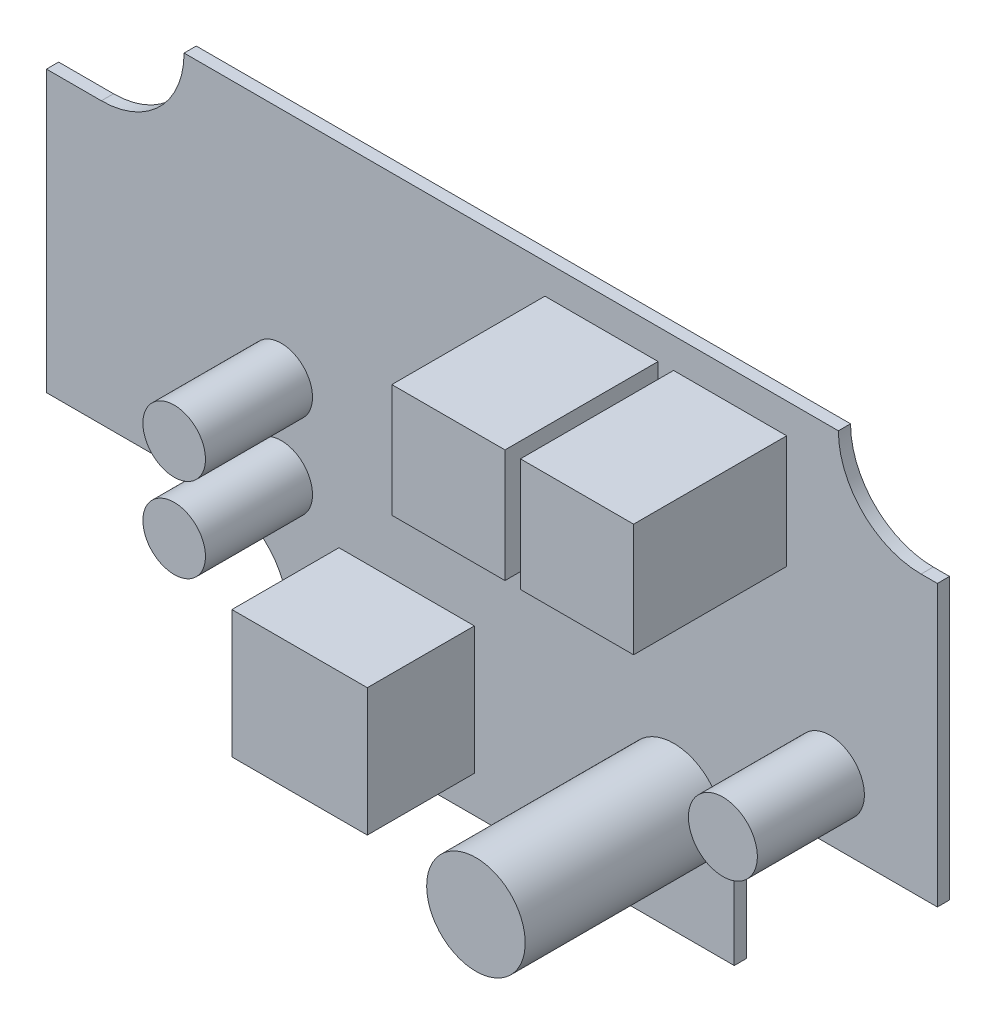
SolidWorks part; units mm, degrees
ref_plane "Front Plane" through (0, 0, 0) normal (0, 0, 1) x (1, 0, 0)
ref_plane "Top Plane" through (0, 0, 0) normal (0, 1, 0) x (1, 0, 0)
ref_plane "Right Plane" through (0, 0, 0) normal (1, 0, 0) x (0, 0, -1)
sketch "Sketch1" plane through (0, 0, 0) normal (0, 0, 1) x (1, 0, 0)
  line L0 (-42.3541, 30.2967) -> (-53.0616, 30.2967) construction
  line L1 (28.8729, -26.0779) -> (28.8729, -36.4043)
  line L2 (-38.257, -16.6937) -> (-60.1693, -16.6937)
  line L3 (-42.3541, 30.2967) -> (42.3541, 30.2967)
  line L4 (38.257, -16.6937) -> (55.1689, -16.6937)
  line L5 (-53.0616, 30.2967) -> (-53.0616, 19.5893) construction
  line L6 (-38.257, -16.6937) -> (-38.257, -26.0779) construction
  line L7 (-38.257, -26.0779) -> (-28.8729, -26.0779) construction
  line L8 (28.8729, -26.0779) -> (38.257, -26.0779) construction
  line L9 (38.257, -26.0779) -> (38.257, -16.6937) construction
  line L10 (53.0616, 19.5893) -> (53.0616, 30.2967) construction
  line L11 (53.0616, 30.2967) -> (42.3541, 30.2967) construction
  line L12 (55.1689, -16.6937) -> (55.1689, 19.5893)
  line L13 (-60.1693, -16.6937) -> (-60.1693, 19.5893)
  line L14 (-60.1693, 19.5893) -> (-53.0616, 19.5893)
  line L15 (55.1689, 19.5893) -> (53.0616, 19.5893)
  line L16 (28.8729, -36.4043) -> (-28.8729, -36.4043)
  line L17 (-28.8729, -36.4043) -> (-28.8729, -26.0779)
  line L18 (-62.1693, -33.1629) -> (-62.1693, 54.0037) construction
  line L19 (65.1689, -33.1629) -> (65.1689, 54.0037) construction
  line L20 (-55.9277, -40.4043) -> (55.9277, -40.4043) construction
  arc A0 (-42.3541, 30.2967) -> (-53.0616, 19.5893) centre (-53.0616, 30.2967) cw
  circle A1 centre (53.0616, 30.2967) radius 1.6 construction
  arc A2 (-38.257, -16.6937) -> (-28.8729, -26.0779) centre (-38.257, -26.0779) cw
  arc A4 (42.3541, 30.2967) -> (53.0616, 19.5893) centre (53.0616, 30.2967) ccw
  arc A5 (38.257, -16.6937) -> (28.8729, -26.0779) centre (38.257, -26.0779) ccw
  circle A8 centre (-53.0616, 30.2967) radius 1.6 construction
  dimension "D1" = 2
  dimension "D2" = 9.3842
  dimension "D3" = 10.7075
  dimension "D4" = 10
  dimension "D5" = 4
extrude "Boss-Extrude1" add sketch "Sketch1" along normal blind 1.5748
sketch "Sketch2" plane through (0, 0, 1.5748) normal (0, 0, 1) x (1, 0, 0)
  line L1 (4.3619, 26.3914) -> (19.0119, 26.3914)
  line L2 (4.3619, 26.3914) -> (4.3619, 11.7414)
  line L3 (4.3619, 11.7414) -> (19.0119, 11.7414)
  line L4 (19.0119, 26.3914) -> (19.0119, 11.7414)
  line L5 (21.0119, 26.3914) -> (35.6619, 26.3914)
  line L6 (21.0119, 26.3914) -> (21.0119, 11.7414)
  line L7 (21.0119, 11.7414) -> (35.6619, 11.7414)
  line L8 (35.6619, 26.3914) -> (35.6619, 11.7414)
  dimension "D1" = 2
  dimension "D2" = 14.65
extrude "Boss-Extrude2" add sketch "Sketch2" along normal blind 19.82
sketch "Sketch3" plane through (0, 0, 1.5748) normal (0, 0, 1) x (1, 0, 0)
  circle A0 centre (21.0509, -21.7791) radius 6.38
  dimension "D1" = 12.76
extrude "Boss-Extrude3" add sketch "Sketch3" along normal blind 25.62
sketch "Sketch4" plane through (0, 0, 1.5748) normal (0, 0, 1) x (1, 0, 0)
  line L1 (-22.3027, -15.1438) -> (-4.7739, -15.1438)
  line L2 (-22.3027, -15.1438) -> (-22.3027, -31.671)
  line L3 (-22.3027, -31.671) -> (-4.7739, -31.671)
  line L4 (-4.7739, -15.1438) -> (-4.7739, -31.671)
  circle A0 centre (-29.7754, 0) radius 4.05
  circle A1 centre (-29.7754, -10.91) radius 4.05
  circle A2 centre (41.2613, -8.8411) radius 4.4585
  dimension "D1" = 8.1
  dimension "D2" = 16.5272
  dimension "D4" = 8.9169
  dimension "D3" = 17.5288
extrude "Boss-Extrude4" add sketch "Sketch4" along normal blind 13.86
